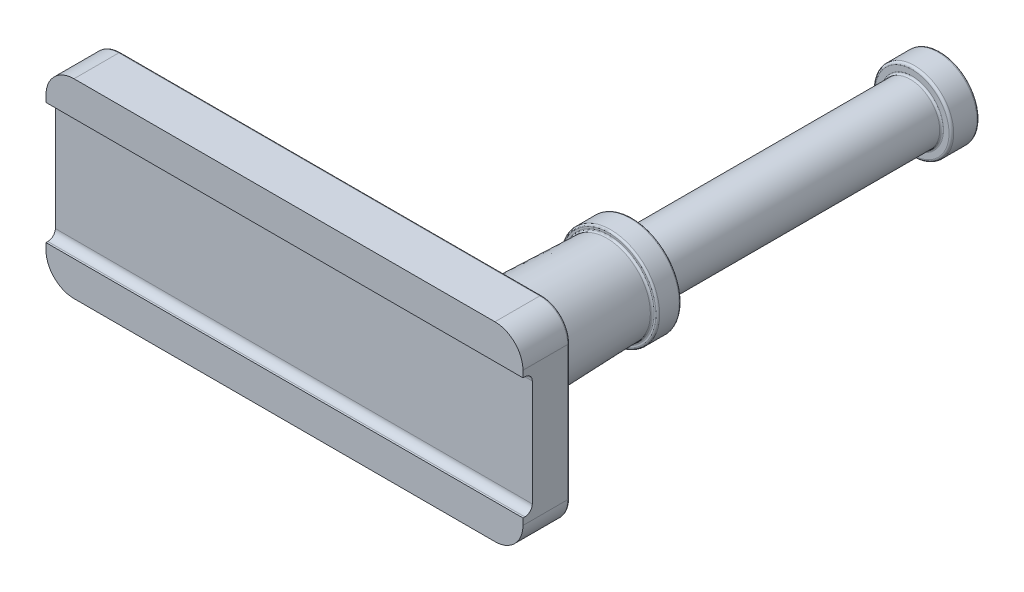
SolidWorks part; units mm, degrees
ref_plane "前视基准面" through (0, 0, 0) normal (0, 0, 1) x (1, 0, 0)
ref_plane "上视基准面" through (0, 0, 0) normal (0, 1, 0) x (1, 0, 0)
ref_plane "右视基准面" through (0, 0, 0) normal (1, 0, 0) x (0, 0, -1)
sketch "Sketch1" plane through (0, 0, 0) normal (0, 0, 1) x (1, 0, 0)
  line L1 (-1277.5, -510) -> (1277.5, -510)
  line L2 (-1277.5, -510) -> (-1277.5, 510)
  line L3 (-1277.5, 510) -> (1277.5, 510)
  line L4 (1277.5, -510) -> (1277.5, 510)
  line L5 (-1277.5, -510) -> (1277.5, 510) construction
  line L6 (-1277.5, 510) -> (1277.5, -510) construction
  point P0 (0, 0)
  dimension "D1" = 2555
  dimension "D2" = 1020
extrude "Extrude1" add sketch "Sketch1" along normal blind 250
fillet "Fillet1" radius 150 4 edges at (1277.5, -510, 125) (-1277.5, -510, 125) (1277.5, 510, 125) (-1277.5, 510, 125)
ref_plane "Plane1" through (762.5, 0, 0) normal (1, 0, 0) x (0, 0, -1)
sketch "Sketch4" plane through (762.5, 0, 0) normal (1, 0, 0) x (0, 0, -1)
  line L0 (0, 0) -> (2500, 0)
  line L1 (0, -360) -> (0, 360) construction
  line L2 (2500, 0) -> (2500, 210)
  line L3 (2500, 210) -> (2350, 210)
  line L4 (2350, 210) -> (2350, 157.5)
  line L5 (2350, 157.5) -> (850, 157.5)
  line L6 (850, 157.5) -> (850, 262.5)
  line L7 (850, 262.5) -> (725, 262.5)
  line L8 (725, 262.5) -> (725, 232.5)
  line L9 (725, 232.5) -> (80, 255.0239)
  line L10 (80, 255.0239) -> (80, 300)
  line L11 (80, 300) -> (0, 300)
  line L12 (0, 300) -> (0, 0)
  line L13 (2500, 0) -> (2810.0618, 0) construction
  dimension "D1" = 2500
  dimension "D2" = 150
  dimension "D3" = 1500
  dimension "D4" = 420
  dimension "D5" = 315
  dimension "D6" = 525
  dimension "D7" = 125
  dimension "D8" = 2
  dimension "D9" = 80
  dimension "D10" = 600
  dimension "D11" = 30
revolve "Revolve1" add sketch "Sketch4" angle 360 about L13
fillet "Fillet2" radius 10 8 edges at (920, 0, -2350) (920, 0, -850) (995, 0, -725) (1025, 0, -725) (1025, 0, -850) (1017.5239, 0, -80) (1062.5, 0, -80) (1062.5, 0, 0)
sketch "Sketch5" plane through (0, 0, 0) normal (0, 0, -1) x (-1, 0, 0)
  line L1 (1127.5, 395) -> (1127.5, 315)
  line L2 (1127.5, 315) -> (1072.5, 260)
  line L3 (1072.5, 260) -> (-290, 260)
  line L4 (-290, 260) -> (-302.5, 272.5)
  line L5 (-302.5, 272.5) -> (-382.5, 272.5)
  line L6 (-382.5, 272.5) -> (-382.5, 222.5)
  line L7 (-382.5, 222.5) -> (-302.5, 222.5)
  line L8 (-302.5, 222.5) -> (-290, 235)
  line L9 (-427.5, 420) -> (-427.5, -420) construction
  line L10 (-1277.5, -360) -> (-1277.5, 360) construction
  line L11 (-290, 235) -> (1072.5, 235)
  line L12 (1127.5, -420) -> (-1127.5, -420)
  line L13 (1187.5, 360) -> (1187.5, -360)
  line L14 (-1127.5, 420) -> (1127.5, 420)
  line L15 (1127.5, -420) -> (-382.5, -420)
  line L16 (1187.5, 360) -> (1187.5, -360)
  line L17 (-382.5, 420) -> (1127.5, 420)
  line L18 (1072.5, 235) -> (1072.5, 95)
  line L19 (1072.5, 95) -> (-290, 95)
  line L20 (-290, 95) -> (-302.5, 107.5)
  line L21 (-302.5, 107.5) -> (-382.5, 107.5)
  line L22 (-382.5, 107.5) -> (-382.5, 57.5)
  line L23 (-382.5, 57.5) -> (-302.5, 57.5)
  line L24 (-302.5, 57.5) -> (-290, 70)
  line L25 (-290, 70) -> (1072.5, 70)
  line L26 (1072.5, 70) -> (1072.5, -70)
  line L27 (1072.5, -70) -> (-290, -70)
  line L28 (-290, -70) -> (-302.5, -57.5)
  line L29 (-302.5, -57.5) -> (-382.5, -57.5)
  line L30 (-382.5, -57.5) -> (-382.5, -107.5)
  line L31 (-382.5, -107.5) -> (-302.5, -107.5)
  line L32 (-302.5, -107.5) -> (-290, -95)
  line L33 (-290, -95) -> (1072.5, -95)
  line L34 (1072.5, -95) -> (1072.5, -235)
  line L35 (1072.5, -235) -> (-290, -235)
  line L36 (-290, -235) -> (-302.5, -222.5)
  line L37 (-302.5, -222.5) -> (-382.5, -222.5)
  line L38 (-382.5, -222.5) -> (-382.5, -272.5)
  line L39 (-382.5, -272.5) -> (-302.5, -272.5)
  line L40 (-302.5, -272.5) -> (-290, -260)
  line L41 (-290, -260) -> (1072.5, -260)
  line L42 (1072.5, -260) -> (1127.5, -315)
  line L43 (1127.5, -315) -> (1127.5, -395)
  line L45 (1127.5, 395) -> (-292.3612, 395)
  line L46 (-292.3612, -395) -> (1127.5, -395)
  arc A0 (-339.8027, -360.7895) -> (-382.5, -420) centre (-382.5, -375) ccw
  arc A1 (-339.8027, -360.7895) -> (-292.3612, -395) centre (-292.3612, -345) ccw
  arc A2 (-292.3612, 395) -> (-339.8027, 360.7895) centre (-292.3612, 345) ccw
  arc A6 (-382.5, 420) -> (-339.8027, 360.7895) centre (-382.5, 375) ccw
  arc A8 (1127.5, -420) -> (1187.5, -360) centre (1127.5, -360) ccw
  arc A9 (1187.5, 360) -> (1127.5, 420) centre (1127.5, 360) ccw
  arc A10 (1127.5, -420) -> (1187.5, -360) centre (1127.5, -360) ccw
  arc A11 (1187.5, 360) -> (1127.5, 420) centre (1127.5, 360) ccw
  dimension "D3" = 90
  dimension "D19" = 100
  dimension "D20" = 100
  dimension "D2" = 850
  dimension "D4" = 45
  dimension "D5" = 45
  dimension "D6" = 45
  dimension "D7" = 45
  dimension "D8" = 45
  dimension "D9" = 45
  dimension "D10" = 45
  dimension "D11" = 45
  dimension "D12" = 45
  dimension "D13" = 45
  dimension "D14" = 25
  dimension "D15" = 45
  dimension "D16" = 25
  dimension "D17" = 50
  dimension "D18" = 80
  dimension "D21" = 25
  dimension "D22" = 140
  dimension "D1" = 90
extrude "Extrude2" cut sketch "Sketch5" against normal blind 150
fillet "Fillet3" radius 20 12 edges at (-1127.5, 315, 75) (-1072.5, 260, 75) (-1072.5, 235, 75) (-1072.5, 95, 75) (-1072.5, 70, 75) (-1072.5, -70, 75) (-1072.5, -95, 75) (-1072.5, -235, 75) (-1072.5, -260, 75) (-1127.5, -315, 75) (-1127.5, 395, 75) (-1127.5, -395, 75)
sketch "Sketch7" plane through (0, 0, 0) normal (0, 0, -1) x (-1, 0, 0)
  line L0 (-557.5, -420) -> (-1127.5, -420)
  line L1 (-1187.5, -360) -> (-1187.5, 360)
  line L2 (-1127.5, 420) -> (-557.5, 420)
  line L3 (-517.5, 380) -> (-517.5, 337.6389)
  line L4 (-517.5, -380) -> (-517.5, -337.6389)
  line L5 (-1277.5, -360) -> (-1277.5, 360) construction
  line L6 (1127.5, -510) -> (-1127.5, -510) construction
  line L7 (-1127.5, 510) -> (1127.5, 510) construction
  arc A0 (-1127.5, -420) -> (-1187.5, -360) centre (-1127.5, -360) cw
  arc A1 (-1187.5, 360) -> (-1127.5, 420) centre (-1127.5, 360) cw
  arc A2 (-578.2595, 303.4476) -> (-578.2595, -303.4476) centre (-762.5, 0) ccw
  arc A6 (-339.8027, -360.7895) -> (-382.5, -420) centre (-382.5, -375) ccw construction
  circle A8 centre (-762.5, 0) radius 310 construction
  arc A9 (-517.5, -337.6389) -> (-578.2595, -303.4476) centre (-557.5, -337.6389) ccw
  arc A10 (-382.5, 420) -> (-339.8027, 360.7895) centre (-382.5, 375) ccw construction
  arc A11 (-557.5, -420) -> (-517.5, -380) centre (-557.5, -380) ccw
  arc A12 (-557.5, 420) -> (-517.5, 380) centre (-557.5, 380) cw
  arc A13 (-517.5, 337.6389) -> (-578.2595, 303.4476) centre (-557.5, 337.6389) cw
  dimension "D6" = 60
  dimension "D7" = 60
  dimension "D8" = 45
  dimension "D9" = 40
  dimension "D1" = 90
  dimension "D2" = 90
  dimension "D3" = 90
  dimension "D4" = 90
  dimension "D5" = 90
extrude "Extrude3" cut sketch "Sketch7" against normal blind 50
fillet "Fillet4" radius 10 90 edges at (-1125.9776, 315.6306, 0) (-1100, 287.5, 0) (-1071.8694, 261.5224, 0) (-387.1079, 260, 0) (296.25, 266.25, 0) (342.5, 272.5, 0) (382.5, 247.5, 0) (342.5, 222.5, 0) (296.25, 228.75, 0) (-381.25, 235, 0) (-1066.6421, 229.1421, 0) (-1072.5, 165, 0) (-1066.6421, 100.8579, 0) (-381.25, 95, 0) (296.25, 101.25, 0) (342.5, 107.5, 0) (382.5, 82.5, 0) (342.5, 57.5, 0) (296.25, 63.75, 0) (-381.25, 70, 0) (-1066.6421, 64.1421, 0) (-1072.5, 0, 0) (-1066.6421, -64.1421, 0) (-381.25, -70, 0) (296.25, -63.75, 0) (342.5, -57.5, 0) (382.5, -82.5, 0) (342.5, -107.5, 0) (296.25, -101.25, 0) (-381.25, -95, 0) (-1066.6421, -100.8579, 0) (-1072.5, -165, 0) (-1066.6421, -229.1421, 0) (-381.25, -235, 0) (296.25, -228.75, 0) (342.5, -222.5, 0) (382.5, -247.5, 0) (342.5, -272.5, 0) (296.25, -266.25, 0) (-387.1079, -260, 0) (-1071.8694, -261.5224, 0) (-1100, -287.5, 0) (-1125.9776, -315.6306, 0) (-1127.5, -349.1421, 0) (-1121.6421, -389.1421, 0) (-407.5694, -395, 0) (321.6061, -385.5554, 0) (418.9998, -348.6796, 0) (-372.5, -420, 0) (-1169.9264, -402.4264, 0) (-1187.5, 0, 0) (-1169.9264, 402.4264, 0) (-372.5, 420, 0) (418.9998, 348.6796, 0) (321.6061, 385.5554, 0) (-407.5694, 395, 0) (-1121.6421, 389.1421, 0) (-1127.5, 349.1421, 0) (1233.566, 466.066, 0) (0, 510, 0) (-1233.566, 466.066, 0) (-1277.5, 0, 0) (-1233.566, -466.066, 0) (0, -510, 0) (1233.566, -466.066, 0) (1277.5, 0, 0) (842.5, -420, 0) (529.2157, -408.2843, 0) (517.5, -358.8194, 0) (537.8834, -302.7793, 0) (1117.5, 0, 0) (537.8834, 302.7793, 0) (517.5, 358.8194, 0) (529.2157, 408.2843, 0) (842.5, 420, 0) (1169.9264, 402.4264, 0) (1187.5, 0, 0) (1169.9264, -402.4264, 0) (1187.5, 0, 50) (1169.9264, 402.4264, 50) (842.5, 420, 50) (529.2157, 408.2843, 50) (517.5, 358.8194, 50) (537.8834, 302.7793, 50) (1117.5, 0, 50) (537.8834, -302.7793, 50) (517.5, -358.8194, 50) (529.2157, -408.2843, 50) (842.5, -420, 50) (1169.9264, -402.4264, 50)
sketch "Sketch8" plane through (1277.5, 0, 0) normal (1, 0, 0) x (0, 0, -1)
  line L0 (0, 0) -> (-355.8382, 0) construction
  line L1 (0, 360) -> (0, -360) construction
  line L2 (-250, 325) -> (-240, 325)
  line L3 (-250, -360) -> (-250, 360) construction
  line L4 (-200, 285) -> (-200, -285)
  line L5 (-240, -325) -> (-250, -325)
  line L6 (-250, -325) -> (-250, 325)
  arc A0 (-240, 325) -> (-200, 285) centre (-240, 285) cw
  arc A1 (-200, -285) -> (-240, -325) centre (-240, -285) cw
  dimension "D3" = 40
  dimension "D4" = 40
  dimension "D1" = 650
  dimension "D2" = 50
extrude "Extrude4" cut sketch "Sketch8" against normal through all
scale "Scale1" bodies to scale 110 scale about centroid uniform scaling yes scale factor 0.8
fillet "Fillet5" radius 10 2 edges at (839.3404, 0, -1941.0003) (839.3404, 0, -2061.0003)
sketch "Sketch10" plane through (0, 0, 138.9997) normal (0, 0, 1) x (1, 0, 0)
  point P0 (671.3404, 0)
sketch "Sketch11" plane through (0, 0, -741.0003) normal (0, 0, -1) x (-1, 0, 0)
  point P0 (-671.3404, 0)
